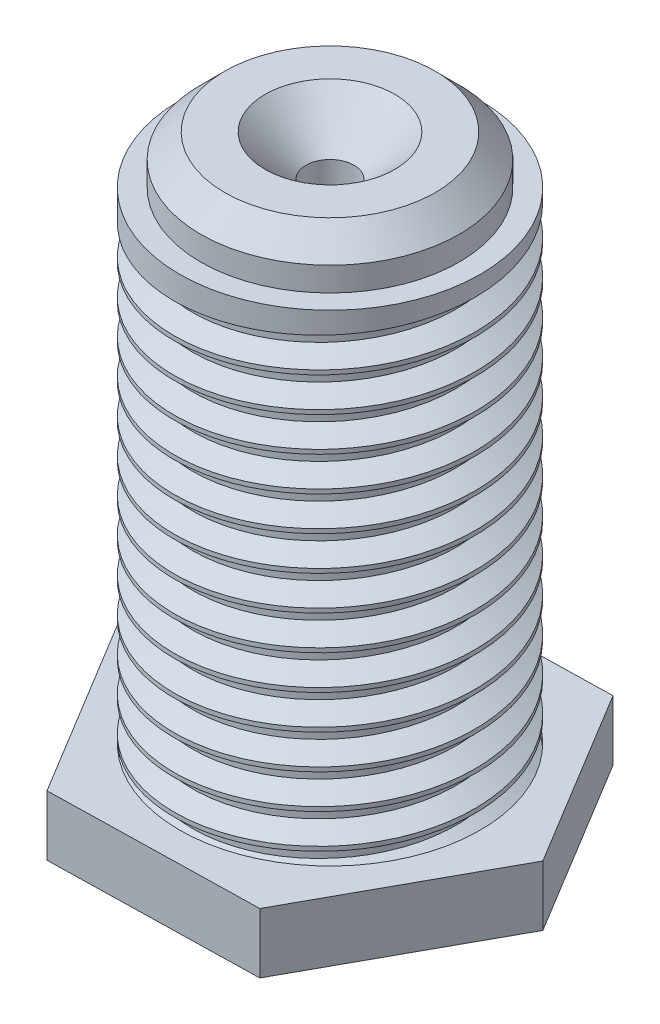
SolidWorks part; units mm, degrees
material "6061-T6 (SS)"
ref_plane "Front Plane" through (0, 0, 0) normal (0, 0, 1) x (1, 0, 0)
ref_plane "Top Plane" through (0, 0, 0) normal (0, 1, 0) x (1, 0, 0)
ref_plane "Right Plane" through (0, 0, 0) normal (1, 0, 0) x (0, 0, -1)
ref_axis "Axis1" through (0, 110.1512, 0) along (0, -1, 0)
sketch "Sketch1" plane through (0, 0, 0) normal (0, 0, 1) x (1, 0, 0)
  line L0 (-15.875, 50.8) -> (-13.6487, 50.8)
  line L1 (-15.875, 0) -> (-15.875, 50.8)
  line L2 (-13.6487, 50.8) -> (-13.6487, 55.88)
  line L3 (-13.6487, 55.88) -> (-6.858, 55.88)
  line L6 (-15.875, 0) -> (0, 0)
  line L8 (0, 110.1512) -> (0, -76.4241) construction
  line L9 (0, 49.022) -> (0, 0)
  line L10 (-6.858, 55.88) -> (0, 49.022)
  dimension "D1" = 15.875
  dimension "D2" = 50.8
  dimension "D3" = 135
  dimension "D4" = 6.858
  dimension "D5" = 13.6487
  dimension "D7" = 5.08
revolve "Revolve1" add sketch "Sketch1" angle 360 about axis through (0, 110.1512, 0) along (0, -1, 0)
cosmetic thread "Cosmetic Thread1" parameters "D2"=27.4295
ref_plane "Plane2" through (0, 110.1512, 0) normal (-1, 0, 0) x (0, 0, 1)
sketch "Sketch12" plane through (0, 0, 0) normal (0, -1, 0) x (1, 0, 0)
  line L1 (-21.992, 0.4698) -> (-11.4029, -18.8107)
  line L2 (-11.4029, -18.8107) -> (10.5891, -19.2806)
  line L3 (10.5891, -19.2806) -> (21.992, -0.4698)
  line L4 (21.992, -0.4698) -> (11.4029, 18.8107)
  line L5 (11.4029, 18.8107) -> (-10.5891, 19.2806)
  line L6 (-10.5891, 19.2806) -> (-21.992, 0.4698)
  circle A0 centre (0, 0) radius 19.05 construction
  dimension "D1" = 38.1
extrude "Boss-Extrude2" add sketch "Sketch12" along normal blind 6.35
ref_plane "Plane4" through (0, 110.1512, 0) normal (-1, 0, 0) x (0, 0, 1)
ref_plane "Plane6" through (0, 110.1512, 0) normal (-1, 0, 0) x (0, 0, 1)
chamfer "Chamfer2" distance 2.54 angle 45 1 edges at (0, 55.88, 13.6487)
thread "Thread1" pitch 3.6286 method cut profile "Thread Profile1" start angle 0, offset 0, length 0, pitch 3.6286, diameter 31.75
ref_plane "Plane7" through (-15.875, 50.8, 0) normal (0, 0, 1) x (-1, 0, 0)
sketch "Thread Profile1" plane through (-15.875, 50.8, 0) normal (0, 0, 1) x (-1, 0, 0)
  line L0 (0, 0) -> (0, 3.6286) construction
  line L11 (0, 0) -> (0, 3.175)
  line L12 (0, 3.175) -> (-1.964, 2.0411)
  line L13 (-1.964, 2.0411) -> (-1.964, 1.1339)
  line L15 (-1.964, 1.1339) -> (0, 0)
  line L17 (-1.964, 1.5875) -> (0, 1.5875) construction
  point P2 (0, 0)
  dimension "Pitch" = 3.6286
  dimension "Profile_Angle" = 60
  dimension "Profile_Land" = 0.9071
  dimension "Profile_Height" = 1.964
sketch "Sketch13" plane through (0, -6.35, 0) normal (0, -1, 0) x (1, 0, 0)
  circle A0 centre (0, 0) radius 2.54
  dimension "D1" = 5.08
extrude "Cut-Extrude1" cut sketch "Sketch13" against normal through all
